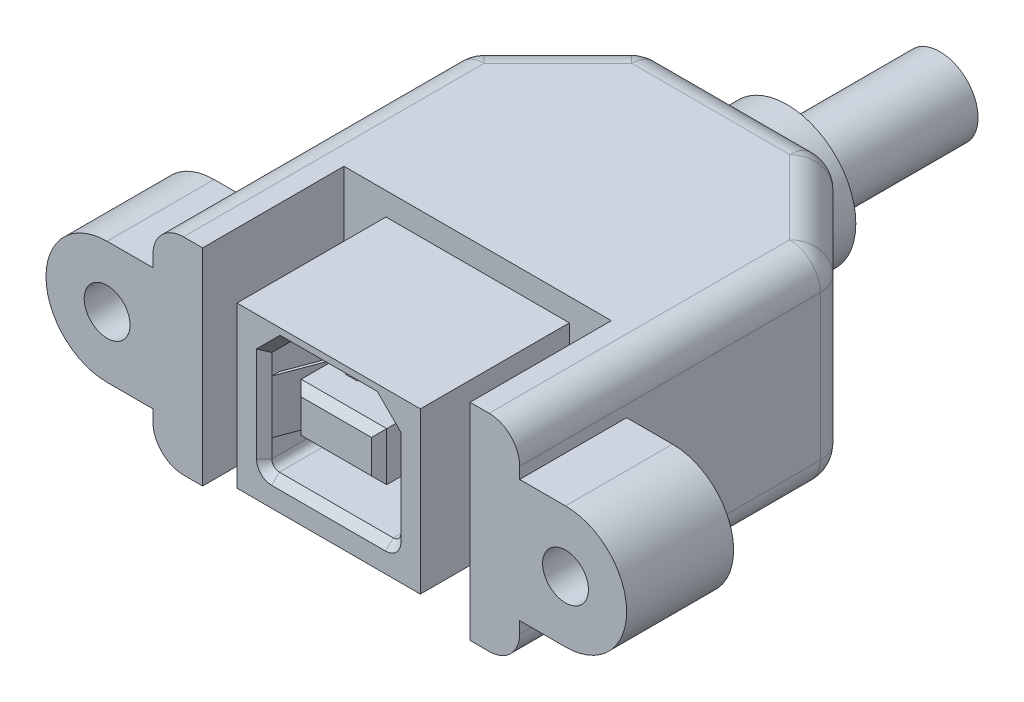
SolidWorks part; units mm, degrees
ref_plane "Front" through (0, 0, 0) normal (0, 0, 1) x (1, 0, 0)
ref_plane "Top" through (0, 0, 0) normal (0, 1, 0) x (1, 0, 0)
ref_plane "Right" through (0, 0, 0) normal (1, 0, 0) x (0, 0, -1)
sketch "Sketch1" plane through (0, 0, 0) normal (0, 0, 1) x (1, 0, 0)
  line L0 (-6, 5.25) -> (6, -5.25) construction
  line L1 (-6, 5.25) -> (6, 5.25)
  line L2 (-6, 5.25) -> (-6, -5.25)
  line L3 (-6, -5.25) -> (6, -5.25)
  line L4 (6, 5.25) -> (6, -5.25)
  dimension "D1" = 12
  dimension "D2" = 10.5
extrude "Base" add sketch "Sketch1" along normal mid plane 16.5
sketch "Sketch2" plane through (0, 0, 8.25) normal (0, 0, 1) x (1, 0, 0)
  line L0 (-2.975, 4.33) -> (-4.225, 3.08)
  line L1 (3.725, -3.45) -> (-3.725, -3.45)
  line L2 (4.225, -2.95) -> (4.225, 3.08)
  line L3 (2.975, 4.33) -> (-2.975, 4.33)
  line L4 (-4.225, -2.95) -> (-4.225, 3.08)
  line L5 (4.225, 3.08) -> (2.975, 4.33)
  line L6 (4.225, 4.33) -> (-4.225, -3.45) construction
  line L7 (6, 5.25) -> (-6, 5.25) construction
  line L9 (0, 0.44) -> (13.9883, 0.44) construction
  arc A0 (-3.725, -3.45) -> (-4.225, -2.95) centre (-3.725, -2.95) cw
  arc A1 (3.725, -3.45) -> (4.225, -2.95) centre (3.725, -2.95) ccw
  point P1 (4.225, 4.33)
  point P2 (-4.225, 4.33)
  point P12 (-4.225, -3.45)
  dimension "D1" = 0.5
  dimension "D2" = 4.81
  dimension "D3" = 8.45
  dimension "D5" = 7.78
extrude "Contact Opening" cut sketch "Sketch2" against normal blind 9
chamfer "Contact Opening Lead-in" distance 0.5 angle 45 8 edges at (-3.6, 3.705, 8.25) (0, 4.33, 8.25) (3.6, 3.705, 8.25) (4.225, 0.065, 8.25) (4.0786, -3.3036, 8.25) (0, -3.45, 8.25) (-4.0786, -3.3036, 8.25) (-4.225, 0.065, 8.25)
sketch "Sketch3" plane through (0, 0, -0.75) normal (0, 0, 1) x (1, 0, 0)
  line L0 (-2.8, 2.03) -> (2.8, -1.15) construction
  line L1 (-2.8, 2.03) -> (2.8, 2.03)
  line L2 (-2.8, 2.03) -> (-2.8, -1.15)
  line L3 (-2.8, -1.15) -> (2.8, -1.15)
  line L4 (2.8, 2.03) -> (2.8, -1.15)
  dimension "D1" = 5.6
  dimension "D2" = 3.18
extrude "Contact Area" add sketch "Sketch3" along normal blind 8.5
chamfer "Contact Area Lead-in" distance 0.5 angle 45 4 edges at (0, 2.03, 7.75) (2.8, 0.44, 7.75) (0, -1.15, 7.75) (-2.8, 0.44, 7.75)
ref_plane "Ground Leg Plane" through (0, 0, -2.15) normal (0, 0, 1) x (1, 0, 0)
sketch "Sketch4" plane through (0, 0, -2.15) normal (0, 0, 1) x (1, 0, 0)
  line L0 (0, 0) -> (0, -12.5407) construction
  line L1 (6.02, -5.058) -> (5.72, -5.1007)
  line L2 (6.4225, -5.35) -> (8.1, -5.35)
  line L3 (8.1, -5.35) -> (8.1, -5.65)
  line L5 (-6.1857, -5.65) -> (-8.1, -5.65)
  line L6 (-8.1, -5.35) -> (-8.1, -5.65)
  line L7 (-6.4225, -5.35) -> (-8.1, -5.35)
  line L8 (-6.02, -5.058) -> (-5.72, -5.1007)
  line L9 (6.1857, -5.65) -> (8.1, -5.65)
  arc A0 (6.02, -5.058) -> (6.4225, -5.35) centre (6.3271, -5.058) ccw
  arc A1 (-5.72, -5.1007) -> (-6.1857, -5.65) centre (-6.3271, -5.058) cw
  arc A2 (-6.02, -5.058) -> (-6.4225, -5.35) centre (-6.3271, -5.058) cw
  arc A5 (5.72, -5.1007) -> (6.1857, -5.65) centre (6.3271, -5.058) ccw
  dimension "D2" = 8.1
  dimension "D3" = 0.3
  dimension "D1" = 10.6
sketch "Sketch7" plane through (0, 0, 0) normal (0, 1, 0) x (1, 0, 0)
  line L0 (-4.225, -7.75) -> (-3.2152, -5.0513)
  line L1 (-3.3072, -2.7298) -> (-3.695, -1.9)
  line L2 (0, 0) -> (0, -8.8202) construction
  line L3 (-3.4657, -2.8039) -> (-3.8535, -1.9741)
  line L4 (-4.3889, -7.6887) -> (-3.3791, -4.99)
  line L5 (-3.695, -1.9) -> (-3.8535, -1.9741)
  line L6 (-4.225, -7.75) -> (-4.3889, -7.6887)
  line L7 (4.225, -7.75) -> (4.3889, -7.6887)
  line L8 (3.695, -1.9) -> (3.8535, -1.9741)
  line L9 (4.3889, -7.6887) -> (3.3791, -4.99)
  line L10 (3.4657, -2.8039) -> (3.8535, -1.9741)
  line L11 (3.3072, -2.7298) -> (3.695, -1.9)
  line L12 (4.225, -7.75) -> (3.2152, -5.0513)
  arc A0 (-3.2152, -5.0513) -> (-3.3072, -2.7298) centre (-6.025, -4) ccw
  arc A1 (-3.3791, -4.99) -> (-3.4657, -2.8039) centre (-6.025, -4) ccw
  arc A2 (3.3791, -4.99) -> (3.4657, -2.8039) centre (6.025, -4) cw
  arc A3 (3.2152, -5.0513) -> (3.3072, -2.7298) centre (6.025, -4) cw
  dimension "D2" = 3
  dimension "D5" = 3.75
  dimension "D1" = 5.85
  dimension "D3" = 1.8
  dimension "D4" = 0.53
  dimension "D6" = 0.175
extrude "Holding Tines" add sketch "Sketch7" along normal mid plane 3.5
ref_plane "Tail Plane" through (0, 0, -7.4) normal (0, 0, -1) x (-1, 0, 0)
ref_plane "Contact Plane" through (-1.25, 0, 0) normal (1, 0, 0) x (0, 0, -1)
ref_plane "SM TAILS PLANE" through (0.75, 0, 0) normal (1, 0, 0) x (0, 0, -1)
sketch "Sketch8" plane through (-1.25, 0, 0) normal (1, 0, 0) x (0, 0, -1)
  line L0 (0.75, 2.03) -> (-2.6953, 2.6783)
  line L1 (-4.4185, 2.4931) -> (-5.75, 1.93)
  line L2 (-7.25, 2.03) -> (0.75, 2.03) construction
  line L3 (0.75, 3.08) -> (0.75, -2.95) construction
  line L4 (-4.3503, 2.3319) -> (-5.6818, 1.7688)
  line L5 (0.7176, 1.858) -> (-2.7276, 2.5063)
  line L6 (0.7176, 1.858) -> (0.75, 2.03)
  line L7 (-5.6818, 1.7688) -> (-5.75, 1.93)
  line L8 (0.75, 2.03) -> (0.75, -1.15) construction
  line L9 (0.75, 0.44) -> (-6.7483, 0.44) construction
  line L10 (-5.6818, -0.8888) -> (-5.75, -1.05)
  line L11 (0.7176, -0.978) -> (0.75, -1.15)
  line L12 (0.7176, -0.978) -> (-2.7276, -1.6263)
  line L13 (-4.3503, -1.4519) -> (-5.6818, -0.8888)
  line L14 (-4.4185, -1.6131) -> (-5.75, -1.05)
  line L15 (0.75, -1.15) -> (-2.6953, -1.7983)
  arc A0 (-2.6953, 2.6783) -> (-4.4185, 2.4931) centre (-3.25, -0.27) ccw
  arc A1 (-2.7276, 2.5063) -> (-4.3503, 2.3319) centre (-3.25, -0.27) ccw
  arc A2 (-2.7276, -1.6263) -> (-4.3503, -1.4519) centre (-3.25, 1.15) cw
  arc A3 (-2.6953, -1.7983) -> (-4.4185, -1.6131) centre (-3.25, 1.15) cw
  dimension "D2" = 3
  dimension "D3" = 2.3
  dimension "D4" = 4
  dimension "D1" = 6.5
  dimension "D5" = 0.1
  dimension "D6" = 0.175
extrude "Contact" add sketch "Sketch8" along normal mid plane 0.75
pattern_linear "Contact Pattern" count 2 spacing 2.5 along (1, 0, 0) of "Contact"
sketch "Sketch16" plane through (0, 0, 0) normal (0, 1, 0) x (1, 0, 0)
  line L0 (-8.75, 1.5) -> (0, 1.5)
  line L1 (-12, 18.75) -> (0, 18.75)
  line L2 (-19, -0.75) -> (-19, -7.75)
  line L3 (-19, -7.75) -> (-8.75, -7.75)
  line L4 (-8.75, 1.5) -> (-8.75, -7.75)
  line L5 (0, 1.5) -> (0, 16.142) construction
  line L6 (6, -8.25) -> (-6, -8.25) construction
  line L7 (-19, -0.75) -> (-12, -0.75)
  line L8 (-12, -0.75) -> (-12, 18.75)
  line L9 (0, 18.75) -> (0, 1.5)
  dimension "D1" = 9.75
  dimension "D2" = 17.5
  dimension "D3" = 27
  dimension "D4" = 0.5
  dimension "D5" = 10.25
  dimension "D6" = 7
  dimension "D7" = 24
extrude "Boss-Extrude1" add sketch "Sketch16" along normal mid plane 13.5 separate body
chamfer "Chamfer1" distance 6 angle 45 1 edges at (-12, 0, -18.75)
sketch "Sketch17" plane through (0, 0, 7.75) normal (0, 0, 1) x (1, 0, 0)
  line L0 (-8.75, 6.75) -> (-8.75, -6.75) construction
  circle A0 centre (-15, 0) radius 1.5
  point P5 (-8.75, 0)
  dimension "D2" = 3
  dimension "D1" = 15
extrude "Cut-Extrude1" cut sketch "Sketch17" against normal through all
sketch "Sketch18" plane through (0, 0, 7.75) normal (0, 0, 1) x (1, 0, 0)
  line L0 (-15, 4) -> (-12, 4)
  line L1 (-12, 4) -> (-12, 6.75)
  line L2 (-19, 6.75) -> (-8.75, 6.75) construction
  line L3 (-15, -4) -> (-12, -4)
  line L4 (-12, -4) -> (-12, -6.75)
  line L5 (-19, -6.75) -> (-8.75, -6.75) construction
  line L6 (-12, -6.75) -> (-19, -6.75)
  line L7 (-19, -6.75) -> (-19, 6.75)
  line L8 (-19, 6.75) -> (-12, 6.75)
  line L10 (-12, 6.75) -> (-12, -6.75) construction
  arc A0 (-15, 4) -> (-15, -4) centre (-15, 0) ccw
  line M2 (-19, -6.75) -> (-8.75, -6.75)
  line M4 (-8.75, 6.75) -> (-19, 6.75)
  line M5 (-19, 6.75) -> (-19, -6.75)
extrude "Cut-Extrude2" cut sketch "Sketch18" against normal through all contours A0 L0 L1 M4 M5 | A0 L7 L4 L3 M2 region at (-15.8946, 5.0316, 7.75) region at (-15.8946, -5.0316, 7.75)
fillet "Fillet1" radius 2 8 edges at (-12, 0, -12.75) (-6, 0, -18.75) (-3, 6.75, -18.75) (-3, -6.75, -18.75) (-12, -6.75, -2.5) (-9, -6.75, -15.75) (-12, 6.75, -2.5) (-9, 6.75, -15.75)
mirror "Mirror1" about plane through (0, 6.75, -18.75) normal (-1, 0, 0) of bodies 120
sketch "Sketch20" plane through (0, 0, -18.75) normal (0, 0, -1) x (-1, 0, 0)
  circle A0 centre (0, 0) radius 4.5
  dimension "D1" = 9
extrude "Boss-Extrude2" add sketch "Sketch20" along normal blind 3
sketch "Sketch21" plane through (0, 0, -21.75) normal (0, 0, -1) x (-1, 0, 0)
  circle A0 centre (0, 0) radius 2.5
  dimension "D1" = 5
extrude "Boss-Extrude3" add sketch "Sketch21" along normal blind 10
combine bodies "Combine1" operation type add bodies to combine 108 123
